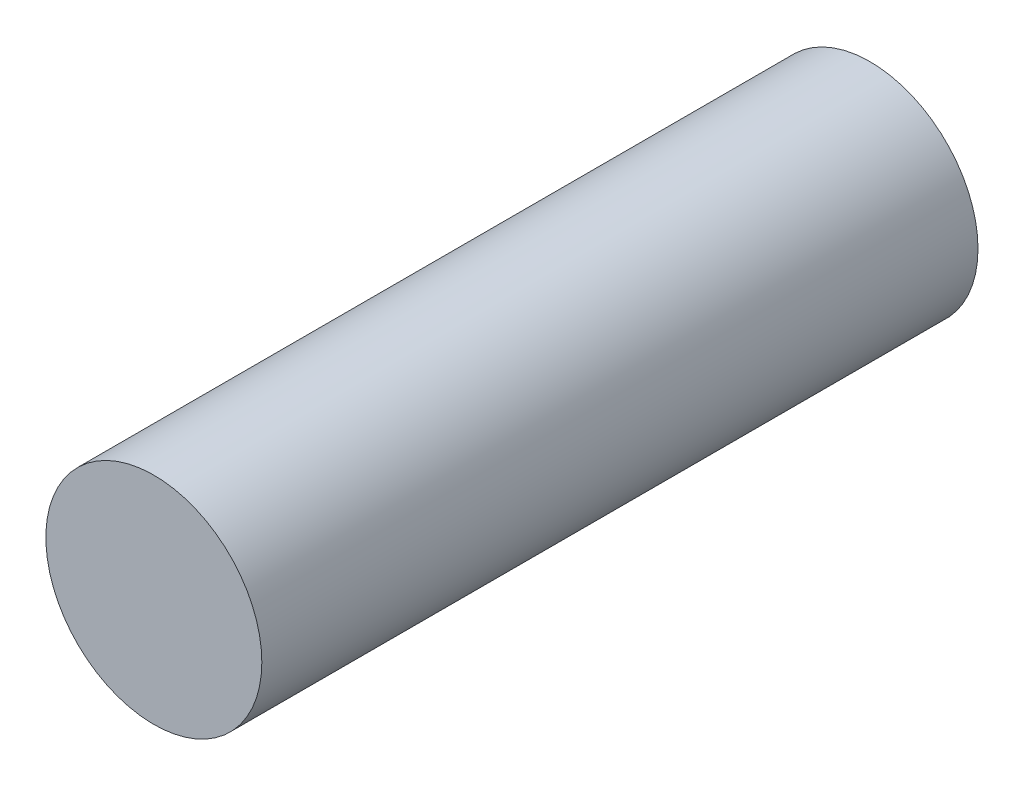
SolidWorks part; units mm, degrees
ref_plane "Front" through (0, 0, 0) normal (0, 0, 1) x (1, 0, 0)
ref_plane "Top" through (0, 0, 0) normal (0, 1, 0) x (1, 0, 0)
ref_plane "Right" through (0, 0, 0) normal (1, 0, 0) x (0, 0, -1)
sketch "ｽｹｯﾁ1" plane through (0, 0, 0) normal (0, 0, 1) x (1, 0, 0)
  circle A0 centre (0, 0) radius 16.15
  dimension "D1" = 32.3
extrude "ﾎﾞｽ - 押し出し1" add sketch "ｽｹｯﾁ1" along normal blind 107.1
